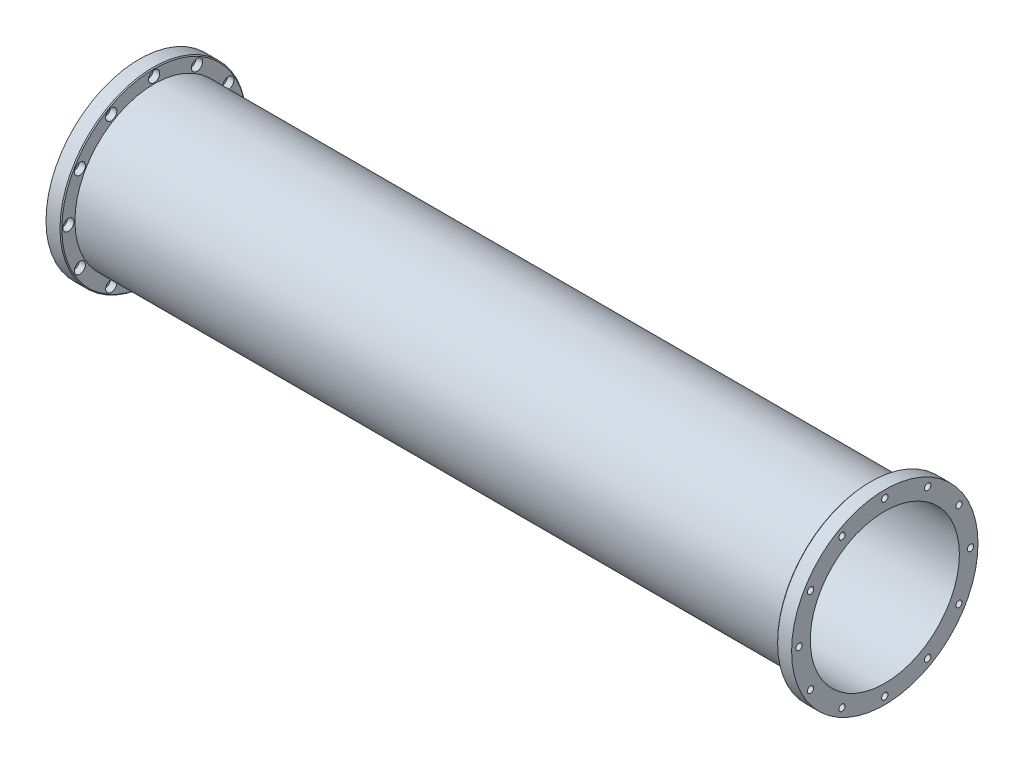
SolidWorks part; units mm, degrees
ref_plane "前视基准面" through (0, 0, 0) normal (0, 0, 1) x (1, 0, 0)
ref_plane "上视基准面" through (0, 0, 0) normal (0, 1, 0) x (1, 0, 0)
ref_plane "右视基准面" through (0, 0, 0) normal (1, 0, 0) x (0, 0, -1)
sketch "草图3" plane through (0, 0, 0) normal (0, 0, 1) x (1, 0, 0)
  line L0 (-303.5533, 0) -> (473.0964, 0) construction
  line L1 (0, 0) -> (0, 50)
  line L2 (0, 50) -> (8, 50)
  line L3 (8, 50) -> (8, 42.5)
  line L4 (8, 42.5) -> (392, 42.5)
  line L5 (392, 42.5) -> (392, 50)
  line L6 (392, 50) -> (400, 50)
  line L7 (400, 50) -> (400, 0)
  line L8 (400, 0) -> (0, 0)
  dimension "D1" = 400
  dimension "D2" = 50
  dimension "D3" = 42.5
  dimension "D4" = 50
  dimension "D5" = 8
  dimension "D6" = 8
revolve "旋转1" add sketch "草图3" angle 360 about L0
sketch "草图4" plane through (400, 0, 0) normal (1, 0, 0) x (0, 0, -1)
  circle A0 centre (0, 0) radius 40
  dimension "D1" = 80
extrude "切除-拉伸1" cut sketch "草图4" against normal through all
hole_wizard "打孔尺寸(%根据)内六角圆柱头螺钉的类型1" positions "草图6" profile "草图5" counterbore size "M3" standard "GB" end condition through all
sketch "草图6" plane through (392, 0, 0) normal (-1, 0, 0) x (0, 0, 1)
  line L0 (0, 0) -> (0, 85.0922) construction
  circle A0 centre (0, 0) radius 46 construction
  point P0 (0, 46)
  dimension "D1" = 92
sketch "草图5" plane through (392, 46, 0) normal (0, 1, 0) x (0, 0, 1)
  line L0 (0, 0) -> (0, 8)
  line L1 (0, 8) -> (1.7, 8)
  line L3 (1.7, 8) -> (1.7, 3.4)
  line L4 (1.7, 3.4) -> (3, 3.4)
  line L5 (3, 3.4) -> (3, 0)
  line L7 (3, 0) -> (0, 0)
  line L11 (0, -6.35) -> (0, 107.95) construction
  dimension "通孔孔直径" = 3.4
  dimension "通孔孔深度" = 8
  dimension "柱形沉头孔直径" = 6
  dimension "柱形沉头孔深度" = 3.4
ref_axis "基准轴1" through (0, 0, 0) along (1, 0, 0)
pattern_circular "阵列(圆周)1" count 12 over 360 about axis through (0, 0, 0) along (1, 0, 0) of "打孔尺寸(%根据)内六角圆柱头螺钉的类型1"
hole_wizard "打孔尺寸(%根据)内六角圆柱头螺钉的类型3" positions "草图10" profile "草图9" counterbore size "M3" standard "GB" end condition through all
sketch "草图10" plane through (8, 0, 0) normal (1, 0, 0) x (0, 0, -1)
  line L0 (0, 0) -> (0, 58.7658) construction
  circle A0 centre (0, 0) radius 46 construction
  point P0 (0, 46)
  dimension "D1" = 92
sketch "草图9" plane through (8, 46, 0) normal (0, 1, 0) x (0, 0, -1)
  line L0 (0, 0) -> (0, 8)
  line L1 (0, 8) -> (1.7, 8)
  line L3 (1.7, 8) -> (1.7, 3.4)
  line L4 (1.7, 3.4) -> (3, 3.4)
  line L5 (3, 3.4) -> (3, 0)
  line L7 (3, 0) -> (0, 0)
  line L11 (0, -6.35) -> (0, 107.95) construction
  dimension "通孔孔直径" = 3.4
  dimension "通孔孔深度" = 8
  dimension "柱形沉头孔直径" = 6
  dimension "柱形沉头孔深度" = 3.4
pattern_circular "阵列(圆周)2" count 12 over 360 about axis through (0, 0, 0) along (1, 0, 0) of "打孔尺寸(%根据)内六角圆柱头螺钉的类型3"
chamfer "倒角1" distance 0.5 angle 45 2 edges at (392, 0, 50) (8, 0, 50)
